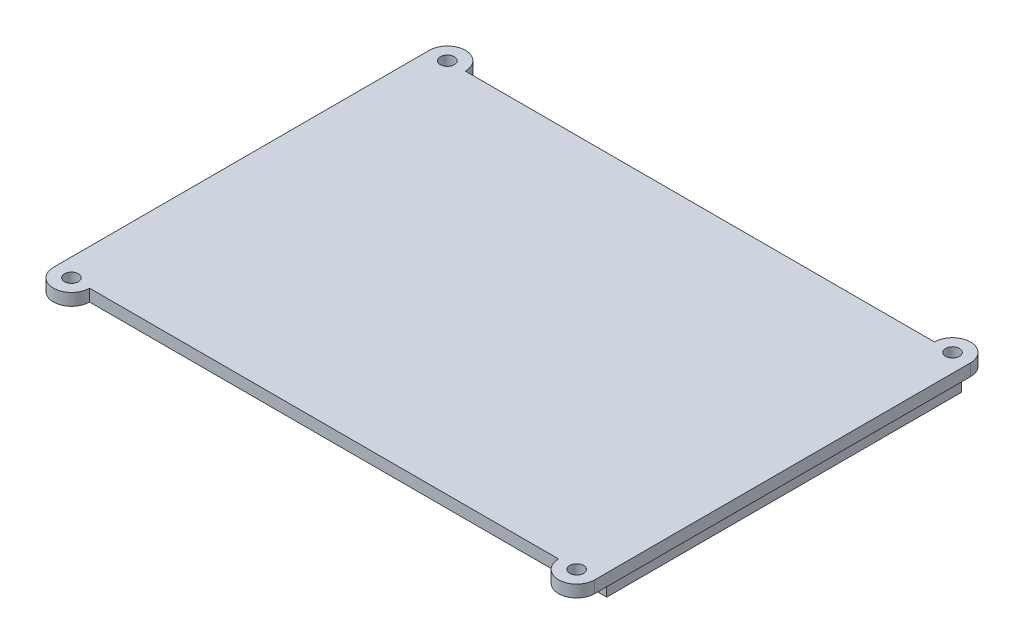
SolidWorks part; units mm, degrees
material "ABS"
ref_plane "Front Plane" through (0, 0, 0) normal (0, 0, 1) x (1, 0, 0)
ref_plane "Top Plane" through (0, 0, 0) normal (0, 1, 0) x (1, 0, 0)
ref_plane "Right Plane" through (0, 0, 0) normal (1, 0, 0) x (0, 0, -1)
sketch "Base" plane through (0, 0, 0) normal (0, 1, 0) x (1, 0, 0)
  line L0 (0, 31.25) -> (90, 31.25) construction
  line L1 (6, 0) -> (84, 0)
  line L2 (0, 0) -> (0, 62.5)
  line L3 (6, 62.5) -> (84, 62.5)
  line L4 (90, 0) -> (90, 62.5)
  line L5 (45, 62.5) -> (45, 0) construction
  arc A0 (0, 62.5) -> (6, 62.5) centre (3, 62.5) cw
  arc A1 (0, 0) -> (6, 0) centre (3, 0) ccw
  arc A2 (90, 0) -> (84, 0) centre (87, 0) cw
  arc A3 (90, 62.5) -> (84, 62.5) centre (87, 62.5) ccw
  point P17 (3, 65.5)
  point P18 (3, -3)
  dimension "D3" = 78
  dimension "D1" = 62.5
  dimension "D2" = 90
  dimension "D4" = 68.5
extrude "Base Extrude" add sketch "Base" along normal blind 2
sketch "Holes" plane through (0, 2, 0) normal (0, 1, 0) x (1, 0, 0)
  line L0 (45, 62.5) -> (45, 0) construction
  line L1 (84, 62.5) -> (6, 62.5) construction
  line L2 (6, 0) -> (84, 0) construction
  line L3 (0, 31.25) -> (90, 31.25) construction
  line L4 (0, 62.5) -> (0, 0) construction
  line L5 (90, 0) -> (90, 62.5) construction
  circle A0 centre (3, 62.5) radius 1.15
  circle A1 centre (87, 62.5) radius 1.15
  circle A2 centre (87, 0) radius 1.15
  circle A3 centre (3, 0) radius 1.15
  dimension "D1" = 2.3
extrude "Holes Cut" cut sketch "Holes" against normal through all
sketch "Sketch3" plane through (0, 0, 0) normal (0, -1, 0) x (1, 0, 0)
  line L1 (2.5, -61.5) -> (89.5, -61.5)
  line L2 (2.5, -61.5) -> (2.5, -2.5)
  line L3 (2.5, -2.5) -> (89.5, -2.5)
  line L4 (89.5, -61.5) -> (89.5, -2.5)
  line L6 (6, 0) -> (84, 0) construction
  line L7 (0, -62.5) -> (0, 0) construction
  dimension "D1" = 59
  dimension "D2" = 87
  dimension "D3" = 2.5
  dimension "D4" = 2.5
extrude "Inside Extrude" add sketch "Sketch3" along normal blind 2
